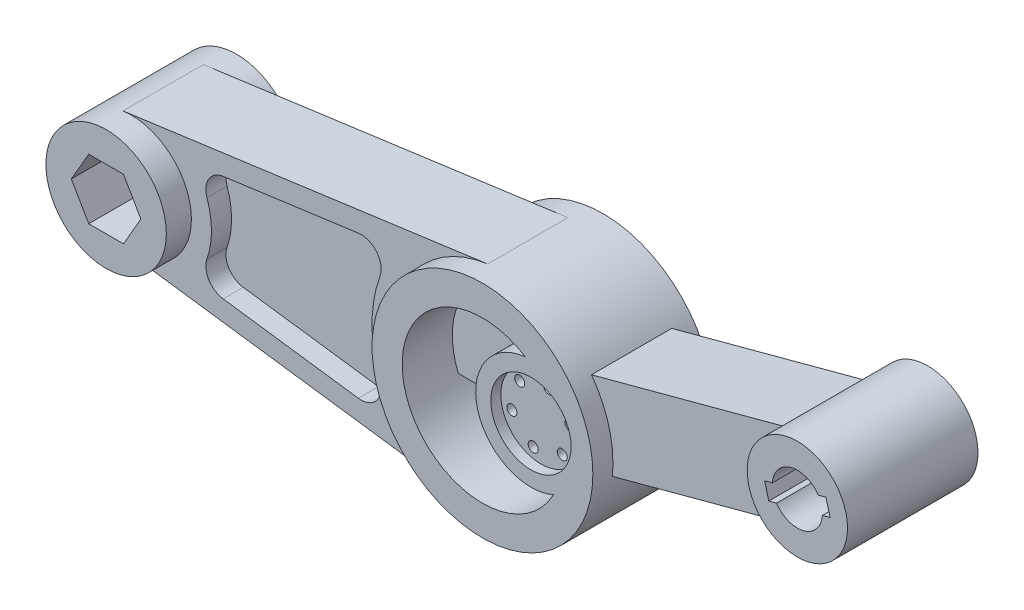
SolidWorks part; units mm, degrees
material "Copper"
ref_plane "Front Plane" through (0, 0, 0) normal (0, 0, 1) x (1, 0, 0)
ref_plane "Top Plane" through (0, 0, 0) normal (0, 1, 0) x (1, 0, 0)
ref_plane "Right Plane" through (0, 0, 0) normal (1, 0, 0) x (0, 0, -1)
ref_plane "CENTRE_Plane" through (185, 0, 0) normal (1, 0, 0) x (0, 0, -1)
ref_axis "CENTRE_Plane_Axis" through (185, 0, 33) along (0, 0, -1)
ref_plane "CENTRE_RIGHT_Plane" through (172.6073, 46.25, 0) normal (0.9659, 0.2588, 0) x (0, 0, -1)
ref_plane "RIGHT_Plane" through (331.9851, 88.9551, 0) normal (0.9659, 0.2588, 0) x (0, 0, -1)
sketch "Sketch1" plane through (0, 0, 0) normal (0, 0, 1) x (1, 0, 0)
  line L0 (-4.0541, 29.7248) -> (177.5676, 54.4955)
  line L1 (-4.0541, -29.7248) -> (177.5676, -54.4955)
  arc A0 (-4.0541, 29.7248) -> (-4.0541, -29.7248) centre (0, 0) ccw
  arc A1 (177.5676, -54.4955) -> (177.5676, 54.4955) centre (185, 0) ccw
  dimension "D1" = 60
  dimension "D2" = 110
extrude "LEFT_ARM" add sketch "Sketch1" along normal mid plane 40
sketch "Sketch2" plane through (0, 0, 0) normal (0, 0, 1) x (1, 0, 0)
  circle A0 centre (0, 0) radius 30
  dimension "D1" = 60
extrude "LEFT_Boss" add sketch "Sketch2" along normal mid plane 65
sketch "Sketch4" plane through (0, 0, 32.5) normal (0, 0, 1) x (1, 0, 0)
  line L0 (35.75, 0) -> (-35.75, 0) construction
  line L1 (17.3205, 0) -> (8.6603, 15)
  line L2 (8.6603, 15) -> (-8.6603, 15)
  line L3 (-8.6603, 15) -> (-17.3205, 0)
  line L4 (-17.3205, 0) -> (-8.6603, -15)
  line L5 (-8.6603, -15) -> (8.6603, -15)
  line L6 (8.6603, -15) -> (17.3205, 0)
  circle A0 centre (0, 0) radius 15 construction
  dimension "D1" = 30
extrude "LEFT_Hex" cut sketch "Sketch4" against normal through all both and the other way through all
sketch "Sketch3" plane through (0, 0, 0) normal (0, 0, 1) x (1, 0, 0)
  circle A0 centre (185, 0) radius 55
  dimension "D1" = 110
extrude "CENTRE_Boss" add sketch "Sketch3" along normal mid plane 60
sketch "Sketch5" plane through (172.6073, 46.25, 0) normal (0.9659, 0.2588, 0) x (0, 0, -1)
  line L0 (-33, -47.8815) -> (33, -47.8815) construction
  line L1 (-20, -67.8815) -> (20, -67.8815)
  line L2 (-20, -67.8815) -> (-20, -27.8815)
  line L3 (-20, -27.8815) -> (20, -27.8815)
  line L4 (20, -67.8815) -> (20, -27.8815)
  line L5 (-20, -67.8815) -> (20, -27.8815) construction
  line L6 (-20, -27.8815) -> (20, -67.8815) construction
  line L7 (0, 67.4878) -> (0, -67.4878) construction
  point P0 (0, -47.8815)
  dimension "D1" = 40
  dimension "D2" = 40
extrude "RIGHT_ARM" add sketch "Sketch5" along normal up to surface (165 mm away) up to plane "RIGHT_Plane"
sketch "RIGHT_ARM_CL" plane through (0, 0, 0) normal (0, 0, 1) x (1, 0, 0)
  line L0 (185, 0) -> (344.3778, 42.7051) construction
  line L1 (347.2915, 31.831) -> (316.6787, 146.0793) construction
sketch "Sketch7" plane through (0, 0, 0) normal (0, 0, 1) x (1, 0, 0)
  circle A0 centre (344.3778, 42.7051) radius 25
  dimension "D1" = 50
extrude "RIGHT_Boss" add sketch "Sketch7" along normal mid plane 65
sketch "Sketch8" plane through (0, 0, 32.5) normal (0, 0, 1) x (1, 0, 0)
  circle A0 centre (344.3778, 42.7051) radius 12.5
  dimension "D1" = 25
extrude "RIGHT_Boss_Hole" cut sketch "Sketch8" against normal through all
sketch "Sketch9" plane through (0, 0, 30) normal (0, 0, 1) x (1, 0, 0)
  circle A0 centre (185, 0) radius 40
  dimension "D1" = 80
extrude "CENTRE_Hole" cut sketch "Sketch9" against normal through all
sketch "Sketch10" plane through (0, 0, 0) normal (0, 0, 1) x (1, 0, 0)
  line L0 (185, 0) -> (344.3778, 42.7051) construction
  line L1 (188.2659, -12.1885) -> (156.9488, 104.6885) construction
  circle A0 centre (209.1481, 6.4705) radius 27.5
  dimension "D1" = 55
  dimension "D2" = 25
extrude "CENTRE_Blob" add sketch "Sketch10" along normal mid plane 60
sketch "Sketch11" plane through (185, 0, 0) normal (1, 0, 0) x (0, 0, -1)
  line L1 (-5, -15) -> (5, -15)
  line L2 (-5, -15) -> (-5, 15)
  line L3 (-5, 15) -> (5, 15)
  line L4 (5, -15) -> (5, 15)
  line L5 (-5, -15) -> (5, 15) construction
  line L6 (-5, 15) -> (5, -15) construction
  point P0 (0, 0)
  dimension "D1" = 10
  dimension "D2" = 30
extrude "CENTRE_Beam" add sketch "Sketch11" along normal up to next and the other way up to next
sketch "Sketch12" plane through (0, 0, 30) normal (0, 0, 1) x (1, 0, 0)
  circle A0 centre (209.1481, 6.4705) radius 20
  dimension "D1" = 40
extrude "Cut-Extrude4" cut sketch "Sketch12" against normal blind 5
hole_wizard "M6x1.0 Tapped Hole1" positions "Sketch13" profile "Sketch14" tap size "M6x1.0" standard "ANSI Metric" end condition up to next
sketch "Sketch13" plane through (0, 0, 25) normal (0, 0, 1) x (1, 0, 0)
  line L0 (185, 0) -> (344.3778, 42.7051) construction
  circle A0 centre (209.1481, 6.4705) radius 20 construction
  point P0 (194.6593, 2.5882)
  dimension "D1" = 15
sketch "Sketch14" plane through (194.6593, 2.5882, 25) normal (1, 0, 0) x (0, -1, 0)
  line L0 (0, 0) -> (0, 55)
  line L1 (0, 55) -> (2.5, 55)
  line L2 (2.5, 55) -> (2.5, 0)
  line L5 (2.5, 0) -> (0, 0)
  line L11 (0, -6.35) -> (0, 107.95) construction
  dimension "Thru Tap Drill Dia." = 5
  dimension "Thru Tap Drill Depth" = 55
cosmetic thread "Hole Thread1" parameters "D2"=6
pattern_circular "CirPattern1" count 6 over 360 about axis through (209.1481, 6.4705, 25) along (0, 0, 1) of "M6x1.0 Tapped Hole1"
cosmetic thread "Hole Thread2" parameters "D2"=6
cosmetic thread "Hole Thread3" parameters "D2"=6
cosmetic thread "Hole Thread4" parameters "D2"=6
cosmetic thread "Hole Thread5" parameters "D2"=6
cosmetic thread "Hole Thread6" parameters "D2"=6
cosmetic thread "Hole Thread7" parameters "D2"=6
cosmetic thread "Hole Thread8" parameters "D2"=6
mirror "Mirror1" about plane through (0, 0, 0) normal (0, 0, 1) of "Cut-Extrude4"
sketch "Sketch15" plane through (0, 0, 20) normal (0, 0, 1) x (1, 0, 0)
  line L24 (132.445, 38.2488) -> (-2.7027, 19.8165)
  line L25 (-2.7027, -19.8165) -> (132.445, -38.2488)
  line L26 (132.445, 38.2488) -> (31.6206, 24.4978)
  line L27 (31.6206, -24.4978) -> (132.445, -38.2488)
  arc A12 (132.445, 38.2488) -> (132.445, -38.2488) centre (185, 0) ccw
  arc A13 (132.445, 38.2488) -> (132.445, -38.2488) centre (185, 0) ccw
  arc A23 (-5.4054, -39.6331) -> (-5.4054, 39.6331) centre (0, 0) ccw
  arc A24 (31.6206, -24.4978) -> (31.6206, 24.4978) centre (0, 0) ccw
  dimension "D1" = 10
  dimension "D2" = 10
extrude "Cut_OUT" cut sketch "Sketch15" against normal blind 10
fillet "Fillet1" radius 10 4 edges at (132.445, 38.2488, 15) (132.445, -38.2488, 15) (31.6206, -24.4978, 15) (31.6206, 24.4978, 15)
mirror "Mirror2" about plane through (0, 0, 0) normal (0, 0, 1) of "Fillet1", "Cut_OUT"
sketch "Sketch16" plane through (0, 0, 0) normal (0, 0, 1) x (1, 0, 0)
  line L0 (345.413, 38.8414) -> (343.3425, 46.5688)
  line L1 (347.2915, 31.831) -> (316.6787, 146.0793) construction
  line L2 (343.3425, 46.5688) -> (328.0809, 42.4795)
  line L3 (328.0809, 42.4795) -> (330.1514, 34.7521)
  line L4 (330.1514, 34.7521) -> (345.413, 38.8414)
  circle A0 centre (344.3778, 42.7051) radius 12.5 construction
  point P4 (344.3778, 42.7051)
  dimension "D1" = 8
  dimension "D2" = 15.8
extrude "KEYWAY" cut sketch "Sketch16" against normal through all both and the other way through all
mirror "Mirror3" about plane through (331.9851, 88.9551, 0) normal (0.9659, 0.2588, 0) of "KEYWAY"
equation "\"D1@Sketch2\"=\"D1@Sketch1\""
equation "\"D1@Sketch3\"=\"D2@Sketch1\""
equation "\"D2@Sketch16\"=12.5+3.3"
